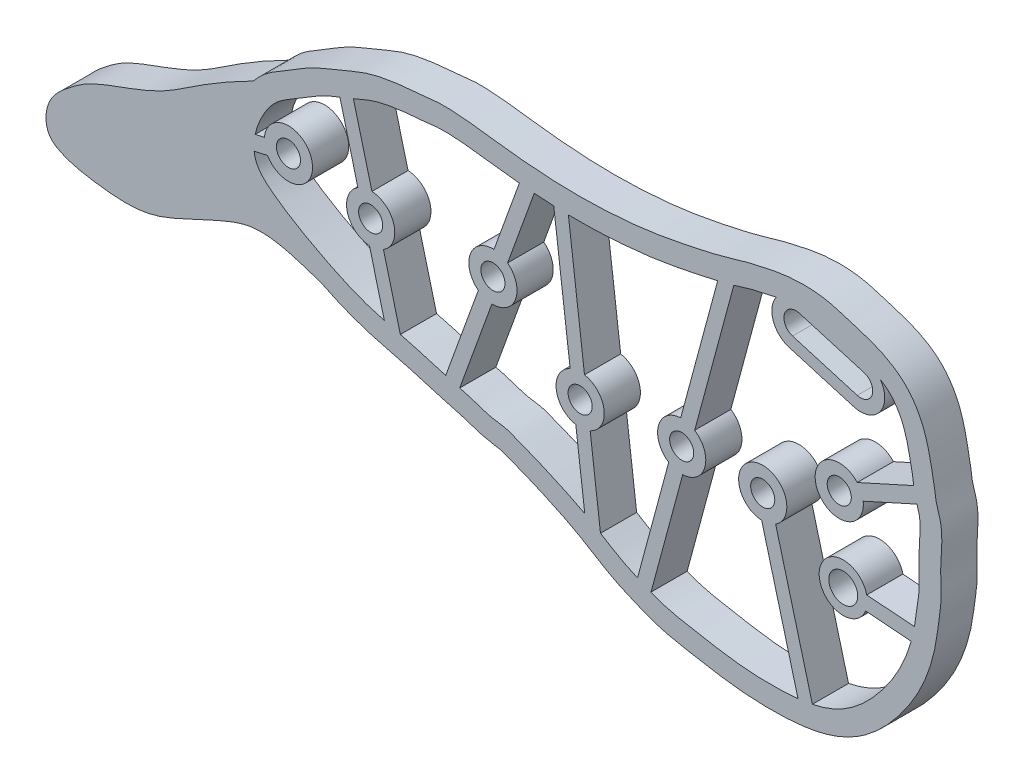
SolidWorks part; units mm, degrees
ref_plane "Спереди" through (0, 0, 0) normal (0, 0, 1) x (1, 0, 0)
ref_plane "Сверху" through (0, 0, 0) normal (0, 1, 0) x (1, 0, 0)
ref_plane "Справа" through (0, 0, 0) normal (1, 0, 0) x (0, 0, -1)
other "Configuration Table"
sketch "Sketch1" plane through (0, 0, 0) normal (0, 0, 1) x (1, 0, 0)
  line L0 (-53.4449, -36.4027) -> (-49.6572, -50.9888) construction
  line L5 (-50.3216, -50.8173) -> (-51.5576, -46.0579)
  line L6 (-52.5163, -42.366) -> (-54.0069, -36.6256)
  line L8 (-51.3548, -42.0644) -> (-52.8865, -36.1659)
  line L9 (-50.3961, -45.7562) -> (-48.9938, -51.1562)
  line L10 (-44.6539, -52.3842) -> (-38.5095, -35.4122) construction
  line L11 (-6.4818, -51.4155) -> (-12.265, -50.9822) construction
  line L12 (-41.2312, -41.1674) -> (-39.127, -35.3552)
  line L14 (-37.8898, -35.4629) -> (-40.1029, -41.5759)
  line L15 (-42.5296, -44.7539) -> (-45.2324, -52.2194)
  line L16 (-41.4013, -45.1624) -> (-44.0733, -52.5428)
  line L17 (-33.0514, -56.7428) -> (-35.6666, -35.5833) construction
  line L18 (-36.274, -35.5605) -> (-34.9137, -46.5669)
  line L19 (-35.0602, -35.5983) -> (-33.7227, -46.4197)
  line L20 (-28.7671, -59.0348) -> (-22.0114, -33.9745) construction
  line L21 (-22.6779, -34.1417) -> (-25.7467, -45.5255)
  line L22 (-21.3407, -33.7919) -> (-24.5881, -45.8379)
  line L23 (-15.4183, -60.7418) -> (-18.9436, -47.5231) construction
  line L24 (-16.018, -60.8216) -> (-19.0319, -49.5205)
  line L25 (-14.8259, -60.6345) -> (-17.8724, -49.2112)
  line L26 (-6.3189, -41.3366) -> (-12.597, -44.1796) construction
  line L27 (-6.4229, -40.7251) -> (-11.1072, -42.8463)
  line L28 (-6.1531, -41.9202) -> (-10.6122, -43.9394)
  line L29 (-16.1872, -34.0479) -> (-10.8235, -35.627) construction
  line L34 (-34.1152, -53.0271) -> (-34.4458, -50.3524) construction
  line L35 (-34.4458, -50.3524) -> (-33.7016, -56.3739)
  line L37 (-33.2549, -50.2052) -> (-32.3983, -57.1358)
  line L43 (-26.7395, -49.2084) -> (-29.3266, -58.8049)
  line L45 (-25.5809, -49.5207) -> (-28.2081, -59.266)
  line L52 (-15.9048, -33.0886) -> (-10.541, -34.6677)
  line L55 (-42.5296, -44.7539) -> (-45.2324, -52.2194) construction
  line L56 (-6.36, -50.823) -> (-10.3184, -50.5264)
  line L57 (-6.36, -50.823) -> (-10.3184, -50.5264)
  line L58 (-16.4697, -35.0072) -> (-11.1059, -36.5863)
  line L59 (-16.1872, -34.0479) -> (-10.8235, -35.627) construction
  line L60 (-15.6224, -32.1293) -> (-10.2586, -33.7084)
  line L61 (-16.7521, -35.9665) -> (-11.3883, -37.5456)
  line L62 (-6.6306, -52.0061) -> (-10.408, -51.723)
  line L63 (-61.1201, -43.4425) -> (-58.2756, -42.8039) construction
  line L64 (-60.2679, -42.6363) -> (-61.0321, -42.8078)
  line L65 (-60.005, -43.8071) -> (-61.1153, -44.0564)
  arc A2 (-50.3961, -45.7562) -> (-51.3548, -42.0644) centre (-51.4562, -44.0611) ccw
  circle A3 centre (-51.4562, -44.0611) radius 1
  arc A4 (-41.4013, -45.1624) -> (-40.1029, -41.5759) centre (-41.3162, -43.1649) ccw
  circle A5 centre (-41.3162, -43.1649) radius 1
  arc A6 (-33.2549, -50.2052) -> (-33.7227, -46.4197) centre (-34.0843, -48.386) ccw
  circle A7 centre (-34.0843, -48.386) radius 1
  arc A8 (-25.5809, -49.5207) -> (-24.5881, -45.8379) centre (-25.6638, -47.5231) ccw
  circle A9 centre (-25.6638, -47.5231) radius 1
  circle A11 centre (-18.9436, -47.5231) radius 1
  arc A14 (-11.1072, -42.8463) -> (-10.6122, -43.9394) centre (-12.597, -44.1796) ccw
  circle A15 centre (-12.597, -44.1796) radius 1
  arc A20 (-17.8724, -49.2112) -> (-19.0319, -49.5205) centre (-18.9436, -47.5231) ccw
  arc A26 (-10.3184, -50.5264) -> (-10.408, -51.723) centre (-12.265, -50.9822) ccw
  circle A29 centre (-12.265, -50.9822) radius 1.2
  arc A30 (-15.9048, -33.0886) -> (-16.4697, -35.0072) centre (-16.1872, -34.0479) ccw
  arc A31 (-11.1059, -36.5863) -> (-10.541, -34.6677) centre (-10.8235, -35.627) ccw
  arc A32 (-52.5163, -42.366) -> (-51.5576, -46.0579) centre (-51.4562, -44.0611) ccw
  arc A33 (-15.6224, -32.1293) -> (-16.7521, -35.9665) centre (-16.1872, -34.0479) ccw
  arc A34 (-11.3883, -37.5456) -> (-10.2586, -33.7084) centre (-10.8235, -35.627) ccw
  arc A37 (-41.2312, -41.1674) -> (-42.5296, -44.7539) centre (-41.3162, -43.1649) ccw
  arc A42 (-34.9137, -46.5669) -> (-34.4458, -50.3524) centre (-34.0843, -48.386) ccw
  arc A47 (-25.7467, -45.5255) -> (-26.7395, -49.2084) centre (-25.6638, -47.5231) ccw
  arc A49 (-56.5864, -44.0651) -> (-56.5834, -44.0611) centre (-58.2756, -42.8039) ccw
  arc A50 (-60.005, -43.8071) -> (-60.2679, -42.6363) centre (-58.2756, -42.8039) ccw
  circle A51 centre (-58.2756, -42.8039) radius 1
  spline S1 degree 3 poles (-58.7581, -48.9922) (-59.7104, -48.3888) (-60.601, -47.7689) (-61.439, -47.0975) (-62.1184, -46.3263) (-62.5768, -45.5944) (-62.8752, -44.6749) (-62.9472, -43.8512) (-62.9111, -43.1163) (-62.7679, -42.2009) (-62.4279, -41.1226) (-61.9297, -40.1381) (-61.4448, -39.3703) (-60.8782, -38.6441) (-60.0099, -37.8528) (-59.0035, -37.2461) (-58.1744, -36.7728) (-57.3271, -36.2387) (-56.3554, -35.6614) (-55.2169, -35.1525) (-54.2864, -34.812) (-53.4311, -34.4398) (-52.4291, -34.0078) (-51.2557, -33.61) (-50.0717, -33.3845) (-49.0452, -33.2306) (-47.8281, -33.1472) (-47.1214, -33.0685) (-45.8394, -32.9) (-44.6534, -32.9307) (-43.5686, -33.0146) (-42.1571, -33.1777) (-40.5095, -33.4038) (-38.5454, -33.6125) (-35.9409, -33.8049) (-33.3406, -33.8329) (-30.7567, -33.6781) (-28.7942, -33.4888) (-26.9201, -33.1962) (-24.9503, -32.8067) (-23.3497, -32.461) (-22.2655, -32.183) (-21.6495, -32.0089) (-21.2094, -31.8775) (-20.7095, -31.7135) (-19.878, -31.4995) (-19.1412, -31.3406) (-18.0288, -31.0843) (-16.5225, -30.8594) (-14.9286, -30.8163) (-13.4817, -31.0389) (-12.6301, -31.275) (-12.133, -31.4395) (-11.6411, -31.5873) (-10.8921, -31.8106) (-9.8671, -32.1394) (-8.5679, -32.7011) (-7.2519, -33.5877) (-6.2079, -34.8676) (-5.5594, -36.216) (-5.2408, -37.3079) (-5.0596, -38.1183) (-4.9425, -38.7029) (-4.8586, -39.1344) (-4.7764, -39.5181) (-4.6916, -40.024) (-4.6394, -40.5082) (-4.5811, -40.8969) (-4.4823, -41.2423) (-4.2813, -41.8514) (-4.1203, -42.6037) (-4.0747, -43.397) (-4.1171, -44.3126) (-4.1787, -45.2836) (-4.1993, -45.9221) (-4.1608, -46.9219) (-4.1506, -47.8891) (-4.2242, -48.6749) (-4.293, -49.0981) (-4.341, -49.3937) (-4.4, -49.8627) (-4.483, -50.5252) (-4.5958, -51.2074) (-4.7781, -52.079) (-5.1851, -53.5482) (-6.0146, -55.4786) (-7.3401, -57.5438) (-8.9971, -59.5041) (-11.088, -61.2325) (-13.7073, -62.3368) (-16.2947, -62.7054) (-18.6823, -62.767) (-21.1287, -62.6183) (-23.0787, -62.3194) (-24.5778, -62.0499) (-25.6889, -61.8523) (-26.8868, -61.6099) (-27.9556, -61.3023) (-28.7638, -60.9861) (-29.2891, -60.7653) (-29.7912, -60.5614) (-30.3561, -60.3273) (-30.9518, -60.0497) (-31.6951, -59.6598) (-32.5624, -59.1498) (-33.5293, -58.5502) (-34.7253, -57.8417) (-36.2969, -57.0762) (-38.0088, -56.3126) (-39.3047, -55.814) (-40.3059, -55.3901) (-40.6535, -55.2776) (-41.0437, -55.2098) (-41.6818, -55.1266) (-42.474, -54.929) (-43.0705, -54.7168) (-43.5262, -54.5599) (-43.9971, -54.425) (-44.7148, -54.2363) (-45.6675, -53.9705) (-47.1182, -53.541) (-48.8494, -53.0287) (-51.0345, -52.5269) (-53.2229, -51.8118) (-54.8479, -51.08) (-56.3053, -50.3685) (-57.5646, -49.6942) (-58.7581, -48.9922) (-59.7104, -48.3888) (-60.601, -47.7689) knots -0.027589 -0.015625 -0.007812 0 0.007812 0.015625 0.019531 0.023437 0.027344 0.03125 0.035156 0.039062 0.046875 0.054687 0.059556 0.063462 0.070312 0.078125 0.085937 0.09375 0.101562 0.109375 0.117187 0.125 0.132812 0.140625 0.148437 0.15625 0.164062 0.171875 0.179687 0.1875 0.195312 0.203125 0.21875 0.234375 0.25 0.28125 0.296875 0.3125 0.328125 0.34375 0.359375 0.367187 0.371094 0.375 0.378906 0.382812 0.390625 0.398437 0.40625 0.421875 0.429687 0.433594 0.4375 0.441406 0.445312 0.453125 0.460937 0.46875 0.476562 0.484375 0.492187 0.496094 0.5 0.503906 0.505859 0.507812 0.511719 0.515625 0.519531 0.523437 0.527344 0.53125 0.535156 0.539062 0.546875 0.554687 0.5625 0.566406 0.568359 0.570312 0.574219 0.578125 0.582031 0.585937 0.59375 0.609375 0.625 0.640625 0.65625 0.671875 0.6875 0.703125 0.71875 0.734375 0.742187 0.75 0.757812 0.765625 0.769531 0.773437 0.777344 0.78125 0.785156 0.789062 0.796875 0.804687 0.8125 0.828125 0.84375 0.851562 0.859375 0.863281 0.867187 0.871094 0.875 0.878906 0.882812 0.886719 0.890625 0.898437 0.90625 0.921875 0.9375 0.953125 0.964598 0.972411 0.984375 0.992187 1 1.007812 1.015625 1.019531 only from (-59.7001, -48.386) to (-59.7001, -48.386)
  spline S2 degree 3 poles (-54.8378, -49.1612) (-57.6604, -47.6241) (-59.8772, -46.0799) (-61.1016, -44.9748) (-61.19, -42.8792) (-60.5369, -41.1939) (-59.2773, -39.4251) (-57.3309, -38.4175) (-55.4721, -37.1478) (-53.2151, -36.3584) (-51.2833, -35.3978) (-49.5351, -35.1222) (-48.3072, -34.966) (-47.2995, -34.9312) (-45.9793, -34.697) (-43.9653, -34.742) (-40.8542, -35.194) (-36.962, -35.5881) (-33.9262, -35.6271) (-31.9892, -35.554) (-30.8887, -35.4887) (-29.5808, -35.3714) (-27.6433, -35.1578) (-24.6742, -34.6016) (-21.912, -33.9992) (-19.9812, -33.3713) (-19.0765, -33.1767) (-17.7192, -32.8438) (-15.8054, -32.5785) (-14.0131, -32.7113) (-11.5739, -33.5264) (-8.8287, -34.1518) (-7.065, -36.9423) (-6.7879, -38.7114) (-6.4527, -40.2945) (-6.4104, -41.2062) (-5.9587, -42.4484) (-5.8567, -43.2131) (-5.9542, -44.844) (-6.0378, -46.2993) (-5.8798, -47.7388) (-6.1409, -49.2063) (-6.4685, -52.3712) (-8.2087, -56.1917) (-12.2182, -60.2134) (-15.6942, -60.8453) (-17.4574, -60.9255) (-18.4504, -60.9397) (-19.983, -60.9127) (-22.1617, -60.661) (-24.8025, -60.1784) (-26.9948, -59.7888) (-28.675, -59.0656) (-30.7159, -58.261) (-33.245, -56.49) (-36.0164, -55.2271) (-37.9357, -54.4025) (-39.0582, -53.9787) (-40.2188, -53.4584) (-41.5664, -53.3759) (-42.8626, -52.8536) (-45.1527, -52.2761) (-48.0976, -51.3224) (-51.3756, -50.6084) (-54.8378, -49.1612) (-57.6604, -47.6241) (-59.8772, -46.0799) knots -0.078621 -0.053539 -0.039111 0 0.008418 0.024992 0.034759 0.054839 0.065896 0.084166 0.104395 0.11788 0.139207 0.153886 0.158466 0.167836 0.177148 0.189373 0.214163 0.249835 0.279723 0.284249 0.294647 0.305206 0.314606 0.339694 0.375025 0.37997 0.386562 0.396484 0.411656 0.431742 0.437535 0.469592 0.482501 0.504001 0.506417 0.516135 0.523104 0.532522 0.536639 0.545133 0.566484 0.569737 0.578233 0.624864 0.662471 0.68872 0.696194 0.699273 0.709375 0.72807 0.744781 0.765339 0.774026 0.78277 0.810922 0.837688 0.846033 0.85436 0.862697 0.872259 0.882004 0.891572 0.921379 0.946461 0.960889 1 1.008418 1.024992 1.034759 only from (-58.7055, -46.8858) to (-58.7055, -46.8858)
  spline S3 degree 3 poles (-61.1941, -39.0539) (-62.626, -39.7821) (-65.2082, -41.2079) (-68.8393, -43.8366) (-72.316, -44.9962) (-74.9893, -46.0569) (-76.7811, -47.3826) (-78.4745, -48.9002) (-78.4678, -51.4704) (-76.4876, -52.5204) (-73.8899, -52.9864) (-69.8015, -53.368) (-66.6063, -51.6264) (-63.7164, -50.3565) (-60.4815, -48.928) (-57.3243, -50.15) (-55.5648, -50.7285) knots 0 0 0 0 0.105046 0.193261 0.291014 0.343614 0.380043 0.43698 0.487582 0.515276 0.574689 0.662804 0.775463 0.804075 0.870738 1 1 1 1
  point P15 (-13.5054, -34.8374)
  point P22 (-13.5054, -34.8374)
  point P47 (-52.8615, -36.1551)
  point P49 (-51.9776, -35.7813)
  point P51 (-47.9143, -51.4155)
  point P55 (-51.5576, -44.0611)
  dimension "D19" = 2
  dimension "D6" = 0.6
  dimension "D10" = 0.6
  dimension "D14" = 0.6
  dimension "D15" = 0.6
  dimension "D11" = 0.6
  dimension "D12" = 0.6
  dimension "D4" = 0.6
  dimension "D5" = 0.6
  dimension "D8" = 0.6
  dimension "D3" = 0.6
  dimension "D9" = 0.6
  dimension "D16" = 0.6
  dimension "D13" = 1
  dimension "D17" = 0.6
  dimension "D18" = 0.6
  dimension "D2" = 0.6
  dimension "D7" = 0.6
extrude "Boss-Extrude2" add sketch "Sketch1" along normal blind 3 contours S1 S2 A33 L60 A34 | S2 L65 A50 L64 | A50 A51 | S2 L6 A32 L5 L9 A2 L8 A3 | S2 L12 A37 L15 L16 A4 L14 A5 | S2 L18 A42 L35 L37 A6 L19 A7 | S2 L21 A47 L43 L45 A8 L22 A9 | S2 L25 A20 L24 A11 | S2 L56 A26 L62 A29 | S2 L27 A14 L28 A15 | S2 A33 L61 A34 A31 L58 A30 L52 | A33 S2 A34 L60 | S1 S3 region at (-50.7866, -48.3979, 0) region at (-43.7053, -48.5503, 0) region at (-61.0565, -43.4339, 0) region at (-34.3133, -46.5096, 0) region at (-27.7753, -54.0761, 0) region at (-17.7361, -52.0481, 0) region at (-10.8571, -51.0859, 0) region at (-13.4094, -33.0375, 0) region at (-16.8137, -32.2432, 0) region at (-11.0372, -43.4711, 0) region at (-68.8436, -47.8458, 0) region at (-62.2466, -44.1119, 0)
equation "\"R small\"= 2"
equation "\"R big\"= 4"
equation "\"width\"= 0.6"
equation "\"D5@Sketch1\"=\"width\""
equation "\"D4@Sketch1\"=\"width\""
equation "\"D3@Sketch1\"=\"width\""
equation "\"D9@Sketch1\"=\"width\""
equation "\"D8@Sketch1\"=\"width\""
equation "\"D6@Sketch1\"=\"width\""
equation "\"D10@Sketch1\"=\"width\""
equation "\"D16@Sketch1\"=\"width\""
equation "\"D11@Sketch1\"=\"width\""
equation "\"D12@Sketch1\"=\"width\""
equation "\"D14@Sketch1\"=\"width\""
equation "\"D15@Sketch1\"=\"width\""
equation "\"border width\"= 1"
equation "\"D13@Sketch1\"=\"border width\""
equation "\"D17@Sketch1\"=\"width\""
equation "\"D18@Sketch1\"=\"width\""
equation "\"depth\"= 3"
equation "\"D2@Sketch1\"=\"width\""
equation "\"D7@Sketch1\"=\"width\""
equation "\"D19@Sketch1\"=\"R small\""
